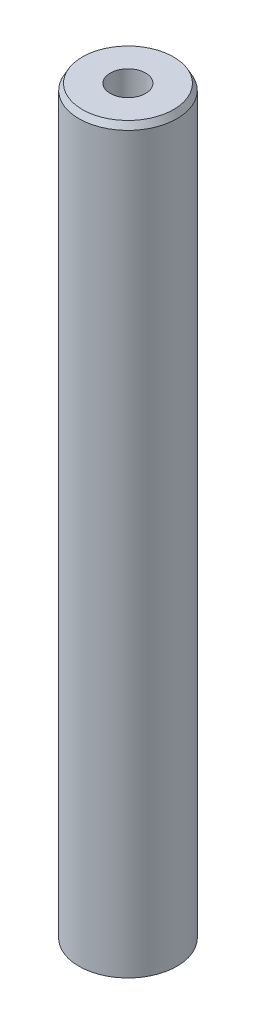
SolidWorks part; units mm, degrees
ref_plane "Front Plane" through (0, 0, 0) normal (0, 0, 1) x (1, 0, 0)
ref_plane "Top Plane" through (0, 0, 0) normal (0, 1, 0) x (1, 0, 0)
ref_plane "Right Plane" through (0, 0, 0) normal (1, 0, 0) x (0, 0, -1)
sketch "Sketch1" plane through (0, 0, 0) normal (0, 1, 0) x (1, 0, 0)
  circle A0 centre (0, 0) radius 5
  dimension "SHAFT_OD" = 10
extrude "Boss-Extrude1" add sketch "Sketch1" along normal blind 75.8287
sketch "Sketch2" plane through (0, 0, 0) normal (0, 1, 0) x (1, 0, 0)
  circle A0 centre (0, 0) radius 1.804
  dimension "BORE_D" = 3.608
extrude "Cut-Extrude1" cut sketch "Sketch2" along normal through all
chamfer "Chamfer1" distance 0.6306 angle 28.963 2 edges at (0, 75.8287, 5) (0, 0, 5) first distance on face at (0, 75.8287, 5) first distance on face at (0, 0, 1.804)
